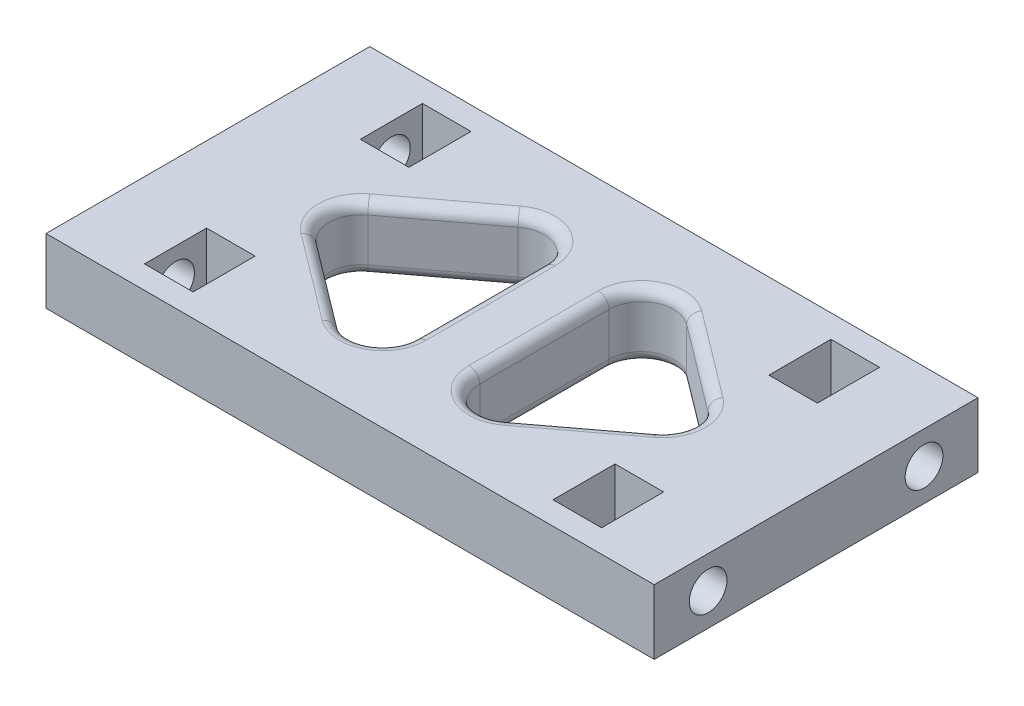
SolidWorks part; units mm, degrees
ref_plane "Front Plane" through (0, 0, 0) normal (0, 0, 1) x (1, 0, 0)
ref_plane "Top Plane" through (0, 0, 0) normal (0, 1, 0) x (1, 0, 0)
ref_plane "Right Plane" through (0, 0, 0) normal (1, 0, 0) x (0, 0, -1)
sketch "Sketch1" plane through (0, 0, 0) normal (1, 0, 0) x (0, 0, -1)
  line L1 (-15, 3) -> (15, 3)
  line L2 (-15, 3) -> (-15, -3)
  line L3 (-15, -3) -> (15, -3)
  line L4 (15, 3) -> (15, -3)
  line L5 (-15, 3) -> (15, -3) construction
  line L6 (-15, -3) -> (15, 3) construction
  point P0 (0, 0)
  dimension "D1" = 30
  dimension "D2" = 6
extrude "Boss-Extrude1" add sketch "Sketch1" along normal mid plane 56.35
sketch "Sketch2" plane through (28.175, 0, 0) normal (1, 0, 0) x (0, 0, -1)
  line L0 (0, 3) -> (0, -3) construction
  line L1 (15, 3) -> (-15, 3) construction
  line L2 (-15, -3) -> (15, -3) construction
  line L3 (-15, 0) -> (15, 0) construction
  line L4 (-15, 3) -> (-15, -3) construction
  line L5 (15, -3) -> (15, 3) construction
  circle A0 centre (-10, 0) radius 1.75
  circle A1 centre (10, 0) radius 1.75
  dimension "D2" = 3.5
  dimension "D1" = 20
extrude "Cut-Extrude1" cut sketch "Sketch2" against normal blind 7
ref_plane "Plane1" through (21.175, 0, 0) normal (1, 0, 0) x (0, 0, -1)
sketch "Sketch3" plane through (21.175, 0, 0) normal (1, 0, 0) x (0, 0, -1)
  line L0 (-12.875, 1.6599) -> (-12.875, 3)
  line L1 (-12.875, -1.6599) -> (-10, -3.3198)
  line L2 (-10, -3.3198) -> (-7.125, -1.6599)
  line L3 (-7.125, -1.6599) -> (-7.125, 1.6599)
  line L4 (-7.125, 1.6599) -> (-10, 3.3198)
  line L5 (-10, 3.3198) -> (-12.875, 1.6599)
  line L6 (-12.875, 1.6599) -> (-12.875, -1.6599)
  line L7 (15, 3) -> (-15, 3) construction
  line L8 (-12.875, 3) -> (-7.125, 3)
  line L9 (-7.125, 3) -> (-7.125, 1.6599)
  line L10 (0, 3) -> (0, -3) construction
  line L11 (-15, -3) -> (15, -3) construction
  line L12 (7.125, 3) -> (7.125, 1.6599)
  line L13 (12.875, 3) -> (7.125, 3)
  line L14 (12.875, 1.6599) -> (12.875, 3)
  line L15 (7.125, -1.6599) -> (7.125, 1.6599)
  line L16 (10, -3.3198) -> (7.125, -1.6599)
  line L17 (12.875, -1.6599) -> (10, -3.3198)
  line L18 (12.875, 1.6599) -> (12.875, -1.6599)
  circle A0 centre (-10, 0) radius 2.875 construction
  dimension "D1" = 5.75
extrude "Cut-Extrude2" cut sketch "Sketch3" against normal blind 4.5 contours L5 L6 L1 L2 L3 L4 | L9 L8 L0 L5 L4 | L18 L14 L13 L12 L15 L16 L17 | L9 L8 L4 region at (21.175, 2.5533, 12.1013) region at (21.175, -0.0193, 10) region at (21.175, 2.5533, 7.8987) region at (21.175, 0.2342, -10)
mirror "Mirror1" about plane through (0, 0, 0) normal (1, 0, 0) of "Cut-Extrude2", "Cut-Extrude1"
sketch "Sketch4" plane through (0, 3, 0) normal (0, 1, 0) x (1, 0, 0)
  line L0 (-28.175, 0) -> (28.175, 0) construction
  line L1 (-28.175, 15) -> (-28.175, -15) construction
  line L2 (28.175, 15) -> (28.175, -15) construction
  line L3 (-18.925, 7.125) -> (-18.925, -7.125) construction
  line L4 (-16.675, 7.125) -> (-21.175, 7.125) construction
  line L6 (0, 15) -> (0, -15) construction
  line L7 (28.175, 15) -> (-28.175, 15) construction
  line L8 (28.175, -15) -> (-28.175, -15) construction
  line L9 (-3, 15) -> (-3, -15)
  line L10 (3, 15) -> (3, -15)
  line L11 (-28.175, 12) -> (28.175, 12) construction
  line L12 (-18.925, 0) -> (-3, 12)
  line L13 (-18.925, 0) -> (-3, -12)
  line L14 (18.925, 0) -> (3, -12)
  line L15 (18.925, 0) -> (3, 12)
  line L16 (-16.675, -7.125) -> (-21.175, -7.125) construction
  point P10 (-18.925, -7.125)
  dimension "D3" = 3
  dimension "D1" = 3
  dimension "D2" = 3
extrude "Cut-Extrude3" cut sketch "Sketch4" against normal through all contours L12 L13 L9 | L14 L15 L10 region at (-8.3083, 3, 0) region at (8.3083, 3, 0)
fillet "Fillet1" radius 3 6 edges at (18.925, 0, 0) (3, 0, 12) (3, 0, -12) (-3, 0, 12) (-18.925, 0, 0) (-3, 0, -12)
fillet "Fillet2" radius 1 24 edges at (16.94, 3, 0) (11.7754, 3, 5.3874) (4.6614, 3, 8.6678) (3, 3, 0) (4.6614, 3, -8.6678) (16.94, -3, 0) (11.7754, -3, 5.3874) (4.6614, -3, 8.6678) (3, -3, 0) (4.6614, -3, -8.6678) (-16.94, -3, 0) (-11.7754, -3, 5.3874) (-4.6614, -3, 8.6678) (-3, -3, 0) (-4.6614, -3, -8.6678) (-16.94, 3, 0) (-11.7754, 3, 5.3874) (-4.6614, 3, 8.6678) (-3, 3, 0) (-4.6614, 3, -8.6678) (11.7754, 3, -5.3874) (11.7754, -3, -5.3874) (-11.7754, -3, -5.3874) (-11.7754, 3, -5.3874)
fillet "Fillet3" radius 0.5 8 edges at (-18.925, -3, -10.5538) (-18.925, -3, -9.4462) (-18.925, -3, 9.4462) (-18.925, -3, 10.5538) (18.925, -3, -9.4462) (18.925, -3, -10.5538) (18.925, -3, 10.5538) (18.925, -3, 9.4462)
